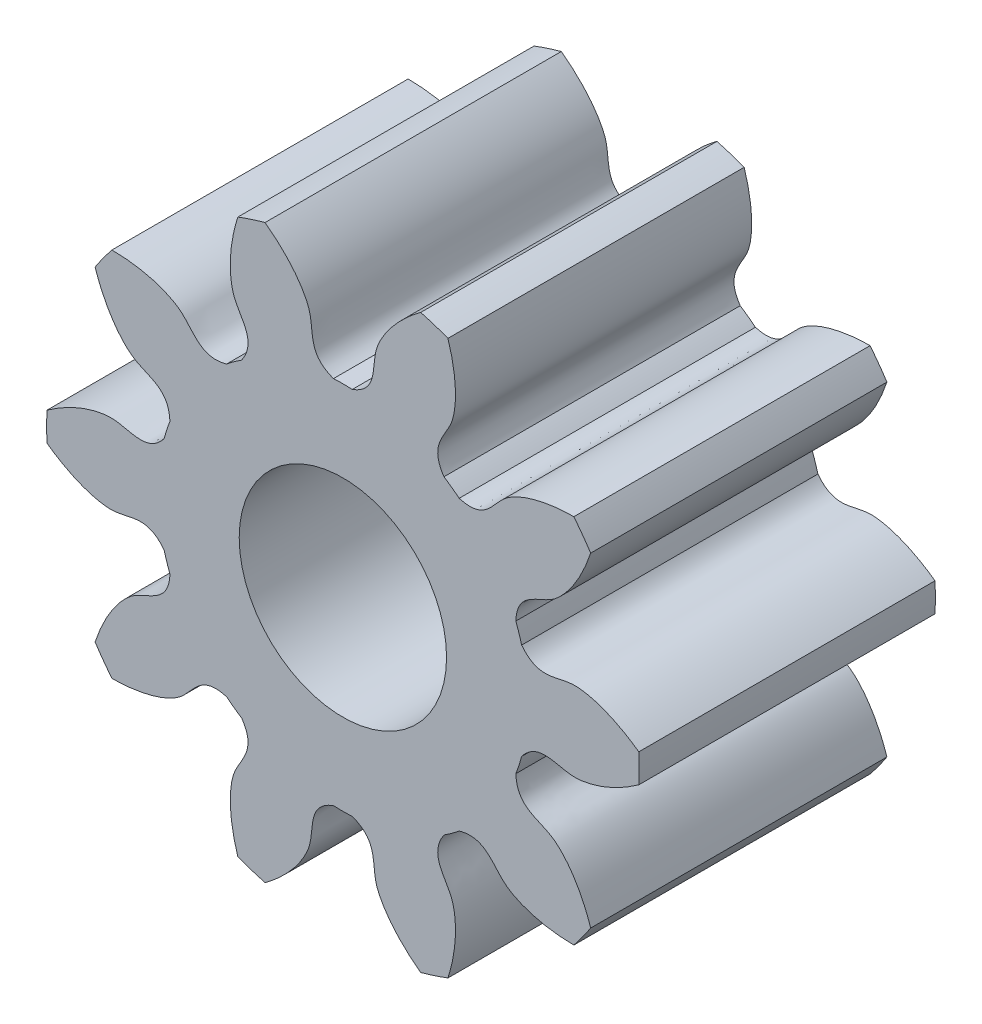
SolidWorks part; units mm, degrees
ref_plane "前视基准面" through (0, 0, 0) normal (0, 0, 1) x (1, 0, 0)
ref_plane "上视基准面" through (0, 0, 0) normal (0, 1, 0) x (1, 0, 0)
ref_plane "右视基准面" through (0, 0, 0) normal (1, 0, 0) x (0, 0, -1)
sketch "草图1" plane through (0, 0, 0) normal (0, 0, 1) x (1, 0, 0)
  circle A0 centre (0, 0) radius 3
extrude "凸台-拉伸1" add sketch "草图1" along normal blind 3
ref_axis "基准轴1" through (0, 0, -0.3) along (0, 0, 1)
sketch "草图2" plane through (0, 0, 0) normal (0, 0, 1) x (1, 0, 0)
  line L0 (0, 0) -> (0, 3) construction
  circle A0 centre (0, 0) radius 3 construction
  arc A1 (0.0952, 1.8726) -> (-0.0952, 1.8726) centre (0, 0) ccw
  arc A2 (2.1268, 3.3471) -> (-2.1268, 3.3471) centre (0, 0) ccw
  spline S0 degree 3 poles (0.0952, 1.8726) (0.3627, 1.9703) (0.2869, 2.1853) (0.3443, 2.3623) (0.3473, 2.3708) (0.3507, 2.38) (0.3546, 2.3901) (0.3591, 2.4009) (0.3642, 2.4126) (0.3699, 2.4249) (0.3763, 2.438) (0.3834, 2.4518) (0.3911, 2.4663) (0.3997, 2.4815) (0.409, 2.4972) (0.4191, 2.5136) (0.4301, 2.5306) (0.4419, 2.5481) (0.4546, 2.5662) (0.4682, 2.5848) (0.4828, 2.6038) (0.4983, 2.6233) (0.5148, 2.6432) (0.5323, 2.6634) (0.5509, 2.684) (0.5705, 2.7049) (0.5911, 2.7261) (0.6129, 2.7476) (0.6358, 2.7692) (0.6598, 2.791) (0.6849, 2.8129) (0.7112, 2.835) (0.7386, 2.8571) (0.7672, 2.8792) (0.7971, 2.9013) (0.8281, 2.9234) (0.8603, 2.9453) (0.8938, 2.9671) (0.9285, 2.9888) (0.9644, 3.0102) (1.0015, 3.0314) (1.0399, 3.0522) (1.0796, 3.0728) (1.1204, 3.0929) (1.1626, 3.1126) (1.2059, 3.1319) (1.2506, 3.1506) (1.2964, 3.1688) (1.3435, 3.1864) (1.3918, 3.2034) (1.4414, 3.2197) (1.4921, 3.2353) (1.5441, 3.2501) (1.5972, 3.2642) (1.6516, 3.2773) (1.7071, 3.2896) (1.7638, 3.301) (1.8216, 3.3114) (1.8805, 3.3208) (1.9405, 3.3291) (2.0227, 3.3388) (2.0849, 3.3443) (2.1268, 3.3471) knots 0 0 0 0 0.201721 0.204697 0.208023 0.211699 0.215726 0.220102 0.224829 0.229906 0.235332 0.241109 0.247237 0.253714 0.260541 0.267719 0.275246 0.283124 0.291352 0.29993 0.308858 0.318136 0.327765 0.337743 0.348072 0.358751 0.36978 0.381158 0.392888 0.404967 0.417396 0.430176 0.443305 0.456785 0.470615 0.484795 0.499325 0.514205 0.529435 0.545016 0.560946 0.577227 0.593858 0.610839 0.62817 0.645851 0.663882 0.682264 0.700995 0.720077 0.739509 0.759291 0.779423 0.799905 0.820737 0.84192 0.863452 0.885335 0.907568 0.930151 0.953084 1 1 1 1
  spline S1 degree 3 poles (-0.0952, 1.8726) (-0.3627, 1.9703) (-0.2869, 2.1853) (-0.3443, 2.3623) (-0.3473, 2.3708) (-0.3507, 2.38) (-0.3546, 2.3901) (-0.3591, 2.4009) (-0.3642, 2.4126) (-0.3699, 2.4249) (-0.3763, 2.438) (-0.3834, 2.4518) (-0.3911, 2.4663) (-0.3997, 2.4815) (-0.409, 2.4972) (-0.4191, 2.5136) (-0.4301, 2.5306) (-0.4419, 2.5481) (-0.4546, 2.5662) (-0.4682, 2.5848) (-0.4828, 2.6038) (-0.4983, 2.6233) (-0.5148, 2.6432) (-0.5323, 2.6634) (-0.5509, 2.684) (-0.5705, 2.7049) (-0.5911, 2.7261) (-0.6129, 2.7476) (-0.6358, 2.7692) (-0.6598, 2.791) (-0.6849, 2.8129) (-0.7112, 2.835) (-0.7386, 2.8571) (-0.7672, 2.8792) (-0.7971, 2.9013) (-0.8281, 2.9234) (-0.8603, 2.9453) (-0.8938, 2.9671) (-0.9285, 2.9888) (-0.9644, 3.0102) (-1.0015, 3.0314) (-1.0399, 3.0522) (-1.0796, 3.0728) (-1.1204, 3.0929) (-1.1626, 3.1126) (-1.2059, 3.1319) (-1.2506, 3.1506) (-1.2964, 3.1688) (-1.3435, 3.1864) (-1.3918, 3.2034) (-1.4414, 3.2197) (-1.4921, 3.2353) (-1.5441, 3.2501) (-1.5972, 3.2642) (-1.6516, 3.2773) (-1.7071, 3.2896) (-1.7638, 3.301) (-1.8216, 3.3114) (-1.8805, 3.3208) (-1.9405, 3.3291) (-2.0227, 3.3388) (-2.0849, 3.3443) (-2.1268, 3.3471) knots 0 0 0 0 0.201721 0.204697 0.208023 0.211699 0.215726 0.220102 0.224829 0.229906 0.235332 0.241109 0.247237 0.253714 0.260541 0.267719 0.275246 0.283124 0.291352 0.29993 0.308858 0.318136 0.327765 0.337743 0.348072 0.358751 0.36978 0.381158 0.392888 0.404967 0.417396 0.430176 0.443305 0.456785 0.470615 0.484795 0.499325 0.514205 0.529435 0.545016 0.560946 0.577227 0.593858 0.610839 0.62817 0.645851 0.663882 0.682264 0.700995 0.720077 0.739509 0.759291 0.779423 0.799905 0.820737 0.84192 0.863452 0.885335 0.907568 0.930151 0.953084 1 1 1 1
extrude "切除-拉伸1" cut sketch "草图2" along normal through all
pattern_circular "阵列(圆周)1" count 10 every 36 about axis through (0, 0, -0.3) along (0, 0, 1) of "切除-拉伸1"
sketch "草图3" plane through (0, 0, 0) normal (0, 0, 1) x (1, 0, 0)
  circle A0 centre (0, 0) radius 2.5 construction
  dimension "Dn" = 5
sketch "草图4" plane through (0, 0, 0) normal (0, 0, -1) x (-1, 0, 0)
  circle A0 centre (0, 0) radius 1.05
  dimension "D1" = 2.1
extrude "切除-拉伸2" cut sketch "草图4" against normal up to next
